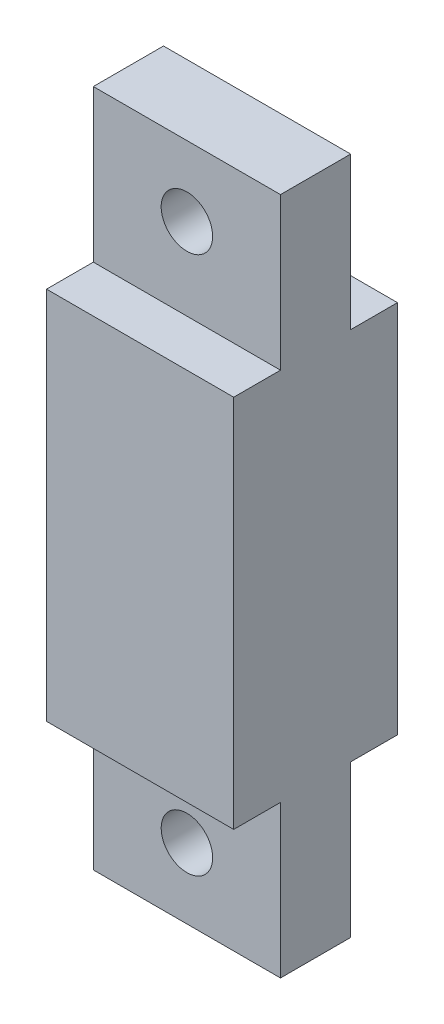
SolidWorks part; units mm, degrees
ref_plane "前视基准面" through (0, 0, 0) normal (0, 0, 1) x (1, 0, 0)
ref_plane "上视基准面" through (0, 0, 0) normal (0, 1, 0) x (1, 0, 0)
ref_plane "右视基准面" through (0, 0, 0) normal (1, 0, 0) x (0, 0, -1)
sketch "草图1" plane through (0, 0, 0) normal (0, 0, 1) x (1, 0, 0)
  line L1 (-4, 14.5) -> (4, 14.5)
  line L2 (-4, 14.5) -> (-4, -14.5)
  line L3 (-4, -14.5) -> (4, -14.5)
  line L4 (4, 14.5) -> (4, -14.5)
  line L5 (-4, 14.5) -> (4, -14.5) construction
  line L6 (-4, -14.5) -> (4, 14.5) construction
  point P0 (0, 0)
  dimension "D1" = 8
  dimension "D2" = 29
extrude "主体" add sketch "草图1" along normal blind 3
sketch "草图2" plane through (0, 0, 0) normal (0, 0, 1) x (1, 0, 0)
  line L0 (4, -14.5) -> (4, 14.5) construction
  line L1 (4, 8) -> (-4, 8)
  line L2 (4, 8) -> (4, -8)
  line L3 (4, -8) -> (-4, -8)
  line L4 (-4, 8) -> (-4, -8)
  line L5 (4, 8) -> (-4, -8) construction
  line L6 (4, -8) -> (-4, 8) construction
  point P0 (0, 0)
  dimension "D1" = 16
extrude "接线柱" add sketch "草图2" against normal blind 2
extrude "触点" add sketch "草图2<2>" along normal blind 2 from surface starting at face at (0, 0, 3)
sketch "草图2<2>" plane through (0, 0, 0) normal (0, 0, 1) x (1, 0, 0) same geometry as "草图2"
sketch "草图3" plane through (0, 0, 3) normal (0, 0, 1) x (1, 0, 0)
  line L0 (0, -3.85) -> (0, 3.85) construction
  line L1 (4, 14.5) -> (-4, 14.5) construction
  line L2 (3.85, 0) -> (-3.85, 0) construction
  circle A0 centre (0, 11.5) radius 1.1
  circle A1 centre (0, -11.5) radius 1.1
  dimension "D1" = 3
extrude "螺丝孔" cut sketch "草图3" against normal up to next
